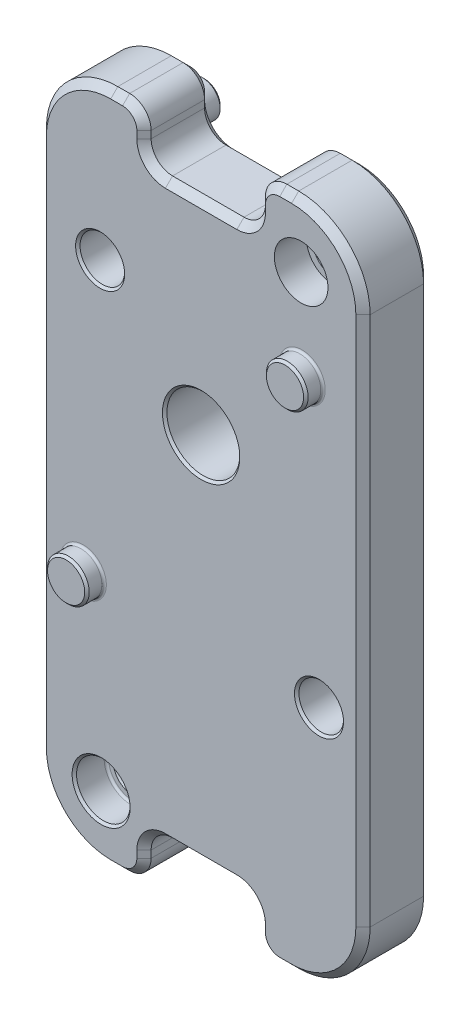
SolidWorks part; units mm, degrees
ref_plane "Front" through (0, 0, 0) normal (0, 0, 1) x (1, 0, 0)
ref_plane "Top" through (0, 0, 0) normal (0, 1, 0) x (1, 0, 0)
ref_plane "Right" through (0, 0, 0) normal (1, 0, 0) x (0, 0, -1)
sketch "Sketch2" plane through (0, 0, 0) normal (0, 0, 1) x (1, 0, 0)
  line L0 (0, 15.3416) -> (0, -37.3507) construction
  line L1 (14.3891, -37.3507) -> (-14.3891, -37.3507)
  line L2 (14.3891, -37.3507) -> (14.3891, 22.4818)
  line L4 (-14.3891, -37.3507) -> (-14.3891, 22.4818)
  line L5 (-15.4933, 0) -> (15.4933, 0) construction
  line L6 (-14.3891, 15.3416) -> (14.3891, 15.3416) construction
  line L7 (-14.3891, 22.4818) -> (14.3891, 22.4818)
  line L8 (-14.3891, -28.0416) -> (14.3891, -28.0416) construction
  line L9 (-14.3891, -31.8516) -> (14.3891, -31.8516) construction
  line L10 (-8.89, 16.9827) -> (-8.89, -31.8516) construction
  line L11 (8.89, 16.9827) -> (8.89, -31.8516) construction
  circle A1 centre (0, 0) radius 3.2385
  arc A2 (-15.4933, 0) -> (15.4933, 0) centre (0, -0.1524) cw construction
  arc A3 (-19.3034, 0) -> (19.3034, 0) centre (0, -0.1524) cw construction
  circle A5 centre (8.89, 16.9827) radius 1.5875
  circle A6 centre (-8.89, -31.8516) radius 1.5875
  point P10 (0, 0)
  dimension "D3" = 15.3416
  dimension "D2" = 15.494
  dimension "D4" = 6.477
  dimension "D6" = 3.81
  dimension "D7" = 3.175
  dimension "D10" = 5.4991
  dimension "D1" = 28.7782
  dimension "D5" = 43.3832
  dimension "D8" = 5.4991
  dimension "D9" = 5.4991
  dimension "D11" = 3.81
  dimension "D12" = 5.4991
extrude "Boss-Extrude1" add sketch "Sketch2" along normal blind 6.0198
sketch "Sketch3" plane through (0, 0, 6.0198) normal (0, 0, 1) x (1, 0, 0)
  circle A0 centre (-8.89, -31.8516) radius 2.3813
  circle A2 centre (8.89, 16.9827) radius 2.3812
  dimension "D1" = 4.7625
extrude "Cut-Extrude1_Counter-sink" cut sketch "Sketch3" against normal blind 2.8448
sketch "Sketch4" plane through (0, 0, 0) normal (0, 0, -1) x (-1, 0, 0)
  line L11 (-8.89, 16.9827) -> (8.89, 16.9827) construction
  line L12 (-8.89, 16.9827) -> (-8.89, -31.8516) construction
  line L13 (-8.89, -31.8516) -> (8.89, -31.8516) construction
  line L14 (8.89, 16.9827) -> (8.89, -31.8516) construction
  circle A0 centre (-8.89, -31.8516) radius 1.5875
  circle A1 centre (8.89, 16.9827) radius 1.5875
  circle A2 centre (-8.89, 16.9827) radius 1.5875 construction
extrude "Boss-Extrude2_BackPegs" add sketch "Sketch4" along normal blind 3.175
sketch "Sketch5" plane through (0, 0, 6.0198) normal (0, 0, 1) x (1, 0, 0)
  line L0 (-10.4775, 22.4818) -> (-10.4775, -37.3507) construction
  line L1 (14.3891, 22.4818) -> (-14.3891, 22.4818) construction
  line L2 (-14.3891, -37.3507) -> (14.3891, -37.3507) construction
  line L3 (10.4775, 22.4818) -> (10.4775, -37.3507) construction
  line L4 (-10.4775, -7.4344) -> (10.4775, -7.4344) construction
  line L5 (0, 0) -> (0, -7.4344) construction
  line L6 (-14.3891, 22.4818) -> (-14.3891, -37.3507) construction
  circle A0 centre (-10.4775, -15.748) radius 1.9812 construction
  circle A1 centre (10.4775, -15.748) radius 1.9812
  circle A2 centre (0, 0) radius 12.7 construction
  circle A3 centre (-8.9789, 8.9816) radius 1.9812
  circle A4 centre (8.9789, 8.9816) radius 1.9812 construction
  dimension "D2" = 3.9624
  dimension "D3" = 25.4
  dimension "D1" = 20.955
  dimension "D4" = 5.4102
  dimension "D5" = 15.748
extrude "Cut-Extrude2_EncoderScrewHoles" cut sketch "Sketch5" against normal through all
sketch "Sketch11" plane through (0, 0, 0) normal (0, 0, -1) x (-1, 0, 0)
  line L0 (14.3891, 22.4818) -> (14.3891, -37.3507) construction
  line L1 (8.9789, 5.6087) -> (11.8999, 7.2952)
  line L2 (11.8999, 7.2952) -> (11.8999, 10.6681)
  line L3 (11.8999, 10.6681) -> (8.9789, 12.3545)
  line L4 (8.9789, 12.3545) -> (6.0579, 10.6681)
  line L5 (6.0579, 10.6681) -> (6.0579, 7.2952)
  line L6 (6.0579, 7.2952) -> (8.9789, 5.6087)
  line L7 (-14.3891, -37.3507) -> (-14.3891, 22.4818) construction
  line L8 (-7.5565, -17.4344) -> (-7.5565, -14.0616)
  line L9 (-7.5565, -14.0616) -> (-10.4775, -12.3751)
  line L10 (-10.4775, -12.3751) -> (-13.3985, -14.0616)
  line L11 (-13.3985, -14.0616) -> (-13.3985, -17.4344)
  line L12 (-13.3985, -17.4344) -> (-10.4775, -19.1209)
  line L13 (-10.4775, -19.1209) -> (-7.5565, -17.4344)
  circle A0 centre (8.9789, 8.9816) radius 2.921 construction
  circle A1 centre (-10.4775, -15.748) radius 2.921 construction
  dimension "D1" = 5.842
extrude "Cut-Extrude4" cut sketch "Sketch11" against normal blind 2.8448
sketch "Sketch6" plane through (0, 0, 6.0198) normal (0, 0, 1) x (1, 0, 0)
  line L0 (-10.4775, 22.4818) -> (-10.4775, -37.3507) construction
  line L1 (10.4775, 22.4818) -> (10.4775, -37.3507) construction
  line L2 (-10.4775, -7.4344) -> (10.4775, -7.4344) construction
  line L3 (0, 0) -> (0, -7.4344) construction
  line L4 (14.3891, 22.4818) -> (-14.3891, 22.4818) construction
  line L5 (-14.3891, -37.3507) -> (14.3891, -37.3507) construction
  line L6 (-14.3891, 22.4818) -> (-14.3891, -37.3507) construction
  circle A0 centre (-10.4775, -15.748) radius 1.8542
  circle A1 centre (10.4775, -15.748) radius 1.8542 construction
  circle A2 centre (0, 0) radius 12.7 construction
  circle A3 centre (-8.9789, 8.9816) radius 1.8542 construction
  circle A4 centre (8.9789, 8.9816) radius 1.8542
  dimension "D2" = 3.7084
  dimension "D3" = 25.4
  dimension "D1" = 20.955
  dimension "D4" = 15.748
  dimension "D5" = 5.4102
extrude "Boss-Extrude3_EncoderPegs" add sketch "Sketch6" along normal blind 1.524
ref_axis "Axis1" through (0, 0, 36.0066) along (0, 0, -1)
ref_plane "Plane1" through (0, 0, 0) normal (0, 1, 0) x (1, 0, 0)
sketch "Sketch8" plane through (0, 0, 0) normal (0, 1, 0) x (1, 0, 0)
  line L0 (0, 7.9624) -> (0, -6.0198) construction
  line L1 (-14.3891, -6.0198) -> (14.3891, -6.0198) construction
  line L2 (-2.3812, 0) -> (-2.3812, 3.175)
  line L3 (-14.3891, 0) -> (14.3891, 0) construction
  line L4 (-2.3812, 3.175) -> (-3.9687, 3.175)
  line L5 (-3.9687, 3.175) -> (-3.9687, 0.1984)
  line L6 (-2.3812, 0) -> (-4.1672, 0)
  arc A0 (-3.9687, 0.1984) -> (-4.1672, 0) centre (-4.1672, 0.1984) cw
  dimension "D1" = 0.1984
  dimension "D2" = 3.175
  dimension "D3" = 1.5875
  dimension "D4" = 2.3813
revolve "Revolve1" [suppressed] add sketch "Sketch8" angle 360 about L0
sketch "Sketch7" plane through (0, 0, 0) normal (0, 0, -1) x (-1, 0, 0)
  line L0 (0, 22.4818) -> (0, -37.3507) construction
  line L1 (-14.3891, 22.4818) -> (14.3891, 22.4818) construction
  line L2 (14.3891, -37.3507) -> (-14.3891, -37.3507) construction
  line L3 (-14.3891, -11.9507) -> (14.3891, -11.9507) construction
  circle A0 centre (0, -11.9507) radius 3.9688
  dimension "D1" = 7.9375
  dimension "D2" = 25.4
extrude "Boss-Extrude4" add sketch "Sketch7" along normal blind 3.175
sketch "Sketch10" plane through (0, 0, 0) normal (0, 0, -1) x (-1, 0, 0)
  line L0 (-8.89, 16.9827) -> (-8.89, -37.3507) construction
  line L1 (-14.3891, 22.4818) -> (14.3891, 22.4818) construction
  line L2 (14.3891, -37.3507) -> (-14.3891, -37.3507) construction
  line L3 (0, 22.4818) -> (0, -37.3507) construction
  line L4 (-8.89, 16.9827) -> (-8.89, 22.4818) construction
  line L6 (-5.08, 22.4818) -> (5.08, 22.4818)
  line L7 (-5.08, 22.4818) -> (-5.08, 18.0368)
  line L8 (-5.08, 18.0368) -> (5.08, 18.0368)
  line L9 (5.08, 22.4818) -> (5.08, 18.0368)
  point P15 (0, 18.0368)
  dimension "D1" = 4.445
  dimension "D2" = 3.81
extrude "Cut-Extrude3" cut sketch "Sketch10" against normal through all
ref_plane "Midplane" through (0, -7.4344, 0) normal (0, -1, 0) x (-1, 0, 0)
mirror "Mirror1" about plane through (0, -7.4344, 0) normal (0, -1, 0) of "Cut-Extrude3"
fillet "Fillet1_0.25" radius 6.35 4 edges at (-14.3891, -37.3507, 3.0099) (14.3891, -37.3507, 3.0099) (14.3891, 22.4818, 3.0099) (-14.3891, 22.4818, 3.0099)
fillet "Fillet5" radius 1.905 4 edges at (-5.08, 22.4818, 3.0099) (5.08, 22.4818, 3.0099) (5.08, -37.3507, 3.0099) (-5.08, -37.3507, 3.0099)
fillet "Fillet4_0.075" radius 1.905 4 edges at (-5.08, 18.0368, 3.0099) (5.08, 18.0368, 3.0099) (-5.08, -32.9057, 3.0099) (5.08, -32.9057, 3.0099)
fillet "Fillet3_1/128" radius 0.1984 30 edges at (-6.5088, -31.8516, 3.175) (7.3025, -31.8516, 0) (-10.4775, 16.9827, 0) (7.1247, 8.9816, 6.0198) (-12.3317, -15.748, 6.0198) (-3.9688, -11.9507, 0) (13.3985, -14.0616, 1.4224) (10.4775, -12.3751, 1.4224) (7.5565, -14.0616, 1.4224) (7.5565, -17.4344, 1.4224) (10.4775, -19.1209, 1.4224) (13.3985, -17.4344, 1.4224) (13.3985, -15.748, 2.8448) (11.938, -13.2183, 2.8448) (9.017, -13.2183, 2.8448) (7.5565, -15.748, 2.8448) (9.017, -18.2777, 2.8448) (11.938, -18.2777, 2.8448) (-8.9789, 5.6087, 1.4224) (-11.8999, 7.2952, 1.4224) (-11.8999, 10.6681, 1.4224) (-8.9789, 12.3545, 1.4224) (-6.0579, 10.6681, 1.4224) (-6.0579, 7.2952, 1.4224) (-6.0579, 8.9816, 2.8448) (-7.5184, 6.452, 2.8448) (-10.4394, 6.452, 2.8448) (-11.8999, 8.9816, 2.8448) (-10.4394, 11.5113, 2.8448) (-7.5184, 11.5113, 2.8448)
chamfer "Chamfer1_0.25" distance 0.635 angle 45 22 edges at (-12.5292, -35.4908, 6.0198) (-14.3891, -7.4344, 6.0198) (-12.5292, 20.6219, 6.0198) (-12.5292, -35.4908, 0) (-14.3891, -7.4344, 0) (-12.5292, 20.6219, 0) (-7.512, 22.4818, 0) (-7.512, 22.4818, 6.0198) (5.08, 20.2593, 0) (4.522, 18.5948, 0) (0, 18.0368, 0) (-4.522, 18.5948, 0) (-5.08, 20.2593, 0) (5.08, 20.2593, 6.0198) (4.522, 18.5948, 6.0198) (0, 18.0368, 6.0198) (-4.522, 18.5948, 6.0198) (-5.08, 20.2593, 6.0198) (5.638, 21.9239, 0) (-5.638, 21.9239, 0) (5.638, 21.9239, 6.0198) (-5.638, 21.9239, 6.0198)
chamfer "Chamfer2_1/128" distance 0.1984 angle 45 39 edges at (-7.3025, -31.8516, 3.175) (3.2385, 0, 0) (3.2385, 0, 6.0198) (10.4775, 16.9827, 0) (-6.9977, 8.9816, 6.0198) (12.4587, -15.748, 6.0198) (7.3025, -31.8516, -3.175) (-10.4775, 16.9827, -3.175) (-8.6233, -15.748, 7.5438) (10.8331, 8.9816, 7.5438) (-7.3025, -31.8516, 0) (-6.5088, -31.8516, 6.0198) (10.4775, 16.9827, 3.175) (-10.9601, 8.9816, 2.8448) (8.4963, -15.748, 2.8448) (-7.5184, 11.5113, 0) (-6.0845, 10.6527, 0) (-8.9789, 12.3238, 0) (-6.0579, 8.9816, 0) (-10.4394, 11.5113, 0) (-6.0845, 7.3105, 0) (-11.8733, 10.6527, 0) (-7.5184, 6.452, 0) (-11.8999, 8.9816, 0) (-8.9789, 5.6394, 0) (-11.8733, 7.3105, 0) (-10.4394, 6.452, 0) (11.938, -13.2183, 0) (13.3719, -14.0769, 0) (10.4775, -12.4058, 0) (13.3985, -15.748, 0) (9.017, -13.2183, 0) (13.3719, -17.4191, 0) (7.5831, -14.0769, 0) (11.938, -18.2777, 0) (7.5565, -15.748, 0) (10.4775, -19.0902, 0) (7.5831, -17.4191, 0) (9.017, -18.2777, 0)
chamfer "Chamfer3_1/64" distance 0.3969 angle 45 1 edges at (-3.9688, -11.9507, -3.175)
